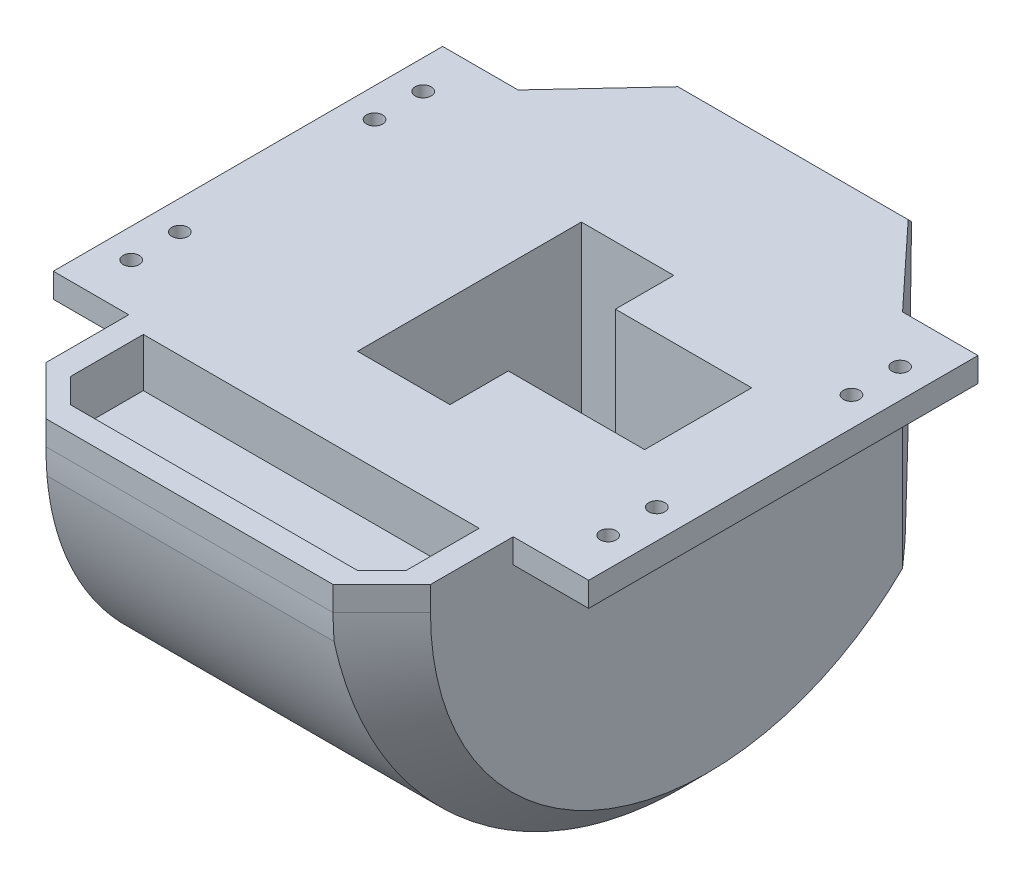
SolidWorks part; units mm, degrees
ref_plane "Front Plane" through (0, 0, 0) normal (0, 0, 1) x (1, 0, 0)
ref_plane "Top Plane" through (0, 0, 0) normal (0, 1, 0) x (1, 0, 0)
ref_plane "Right Plane" through (0, 0, 0) normal (1, 0, 0) x (0, 0, -1)
sketch "Sketch2" plane through (0, 0, 0) normal (0, 1, 0) x (1, 0, 0)
  line L0 (0, 0) -> (16.0378, 0) construction
  line L1 (-55, 40) -> (55, 40)
  line L2 (-55, 40) -> (-55, -40)
  line L3 (-55, -40) -> (55, -40)
  line L4 (55, 40) -> (55, -40)
  line L5 (-55, 40) -> (55, -40) construction
  line L6 (-55, -40) -> (55, 40) construction
  line L7 (0, 15.2625) -> (0, 0) construction
  line L8 (9.5, -11) -> (9.5, -23)
  line L9 (-9.5, 23) -> (9.5, 23)
  line L10 (-9.5, 23) -> (-9.5, -23)
  line L11 (-9.5, -23) -> (9.5, -23)
  line L12 (9.5, 23) -> (9.5, 11)
  line L13 (-9.5, 23) -> (9.5, -23) construction
  line L14 (-9.5, -23) -> (9.5, 23) construction
  line L15 (9.5, 11) -> (37.5, 11)
  line L17 (9.5, -11) -> (37.5, -11)
  line L18 (37.5, 11) -> (37.5, -11)
  circle A0 centre (-49, 30) radius 1.65
  circle A1 centre (-49, 20) radius 1.65
  circle A2 centre (49, 20) radius 1.65
  circle A3 centre (49, 30) radius 1.65
  circle A4 centre (49, -30) radius 1.65
  circle A5 centre (49, -20) radius 1.65
  circle A6 centre (-49, -30) radius 1.65
  circle A7 centre (-49, -20) radius 1.65
  point P0 (0, 0)
  dimension "D3" = 3.3
  dimension "D4" = 10
  dimension "D5" = 6
  dimension "D7" = 10
  dimension "D8" = 19
  dimension "D1" = 110
  dimension "D2" = 80
  dimension "D9" = 46
  dimension "D10" = 12
  dimension "D11" = 12
  dimension "D12" = 28
  dimension "D6" = 2
extrude "Boss-Extrude1" add sketch "Sketch2" along normal blind 5
sketch "Sketch4" plane through (0, 5, 0) normal (0, 1, 0) x (1, 0, 0)
  line L0 (55, 40) -> (-55, 40) construction
  line L1 (-39.5, 40) -> (39.5, 40)
  line L2 (-39.5, 40) -> (-39.5, 67)
  line L3 (-39.5, 67) -> (39.5, 67)
  line L4 (39.5, 40) -> (39.5, 67)
  line L10 (-9.5, 23) -> (-9.5, -23) construction
  line L11 (9.5, 11) -> (9.5, 23) construction
  line L12 (0, 0) -> (48.9802, 0) construction
  line L13 (39.5, -40) -> (39.5, -67)
  line L14 (-39.5, -67) -> (39.5, -67)
  line L15 (-39.5, -40) -> (-39.5, -67)
  line L16 (-39.5, -40) -> (39.5, -40)
  dimension "D1" = 30
  dimension "D2" = 30
  dimension "D3" = 27
extrude "Boss-Extrude2" add sketch "Sketch4" against normal blind 5
sketch "Sketch6" plane through (-39.5, 0, 0) normal (-1, 0, 0) x (0, 0, 1)
  line L0 (67, 0) -> (-67, 0) construction
  line L1 (-67, 0) -> (67, 0)
  arc A0 (-67, 0) -> (67, 0) centre (0, 0) ccw
extrude "Boss-Extrude3" add sketch "Sketch6" against normal blind 79
sketch "Sketch7" plane through (0, 0, 0) normal (0, 1, 0) x (1, 0, 0)
  line L1 (-9.5, -23) -> (9.5, -23)
  line L2 (-9.5, -23) -> (-9.5, 23)
  line L3 (-9.5, 23) -> (9.5, 23)
  line L4 (9.5, -23) -> (9.5, 23)
  line L5 (-9.5, -23) -> (9.5, 23) construction
  line L6 (-9.5, 23) -> (9.5, -23) construction
  line L7 (9.5, 11) -> (37.5, 11)
  line L8 (9.5, 11) -> (9.5, -11)
  line L9 (9.5, -11) -> (37.5, -11)
  line L10 (37.5, 11) -> (37.5, -11)
  point P0 (0, 0)
  line M1 (-9.5, 23) -> (-9.5, -23)
  line M2 (-9.5, -23) -> (9.5, -23)
  line M3 (9.5, -23) -> (9.5, -11)
  line M4 (9.5, -11) -> (37.5, -11)
  line M5 (37.5, -11) -> (37.5, 11)
  line M6 (37.5, 11) -> (9.5, 11)
  line M7 (9.5, 11) -> (9.5, 23)
  line M8 (9.5, 23) -> (-9.5, 23)
extrude "Cut-Extrude1" cut sketch "Sketch7" against normal blind 55.5 contours L4 M4 M5 M6 | L4 M3 M7 M8 M1 M2 region at (0, 0, 0) region at (23.5, 0, 0)
chamfer "Chamfer1" distance 10 angle 45 6 edges at (39.5, 2.5, -67) (39.5, 2.5, 67) (39.5, -67, 0) (-39.5, 2.5, -67) (-39.5, 2.5, 67) (-39.5, -67, 0)
sketch "Sketch8" plane through (0, 5, 0) normal (0, 1, 0) x (1, 0, 0)
  line L0 (-29.5, -67) -> (29.5, -67) construction
  line L1 (-34.5, -42) -> (34.5, -42)
  line L2 (-34.5, -42) -> (-34.5, -57)
  line L3 (-29.5, -62) -> (29.5, -62)
  line L4 (34.5, -42) -> (34.5, -57)
  line L5 (39.5, -57) -> (39.5, -40) construction
  line L6 (-39.5, -40) -> (-39.5, -57) construction
  line L7 (-34.5, -57) -> (-29.5, -62)
  line L8 (29.5, -62) -> (34.5, -57)
  line L9 (0, 0) -> (68.0281, 0) construction
  point P1 (34.5, -62)
  point P2 (-34.5, -62)
  point P23 (-34.5, 62)
  point P24 (34.5, 62)
  dimension "D1" = 5
  dimension "D2" = 20
  dimension "D3" = 5
  dimension "D4" = 5
extrude "Cut-Extrude2" cut sketch "Sketch8" against normal blind 10
sketch "Sketch10" plane through (-39.5, 0, 0) normal (-1, 0, 0) x (0, 0, 1)
  line L0 (-40, 5) -> (40, 5) construction
  line L1 (-72.5766, 5) -> (72.5766, 5)
  circle A0 centre (0, 5) radius 72.5766
  circle A1 centre (0, 5) radius 67.5766
  dimension "D1" = 5
extrude "Cut-Extrude4" cut sketch "Sketch10" against normal through all contours A1 L1 A0 region at (-39.5, 3.3771, 70.0766)
chamfer "Chamfer2" distance 10 angle 45 1 edges at (0, 5, -67)
sketch "Sketch12" plane through (0, 5, 0) normal (0, 1, 0) x (1, 0, 0)
  line L0 (39.5, 40) -> (14.5, 66.826)
  line L1 (-29.5, 66.826) -> (29.5, 66.826) construction
  line L2 (14.5, 66.826) -> (-14.5, 66.826)
  line L3 (-14.5, 66.826) -> (-39.5, 40)
  line L5 (39.5, 40) -> (39.5, 57) construction
  line L6 (-39.5, 57) -> (-39.5, 40) construction
  line L9 (39.5, 40) -> (-39.5, 40)
  line L10 (39.5, 40) -> (39.5, 66.826)
  line L11 (39.5, 66.826) -> (-39.5, 66.826)
  line L12 (-39.5, 40) -> (-39.5, 66.826)
  line M12 (39.5, 40) -> (39.5, 57)
  line M13 (39.5, 57) -> (-39.5, 57)
  line M14 (-39.5, 57) -> (-39.5, 40)
  dimension "D1" = 25
  dimension "D2" = 25
extrude "Cut-Extrude5" cut sketch "Sketch12" against normal through all contours L0 M12 M13 | L3 M13 M14 | L12 L3 L11 M13 | L10 L11 L0 M13 region at (34.219, 5, -51.3333) region at (29.1182, 5, -62.2802) region at (-34.219, 5, -51.3333) region at (-29.1182, 5, -62.2802)
